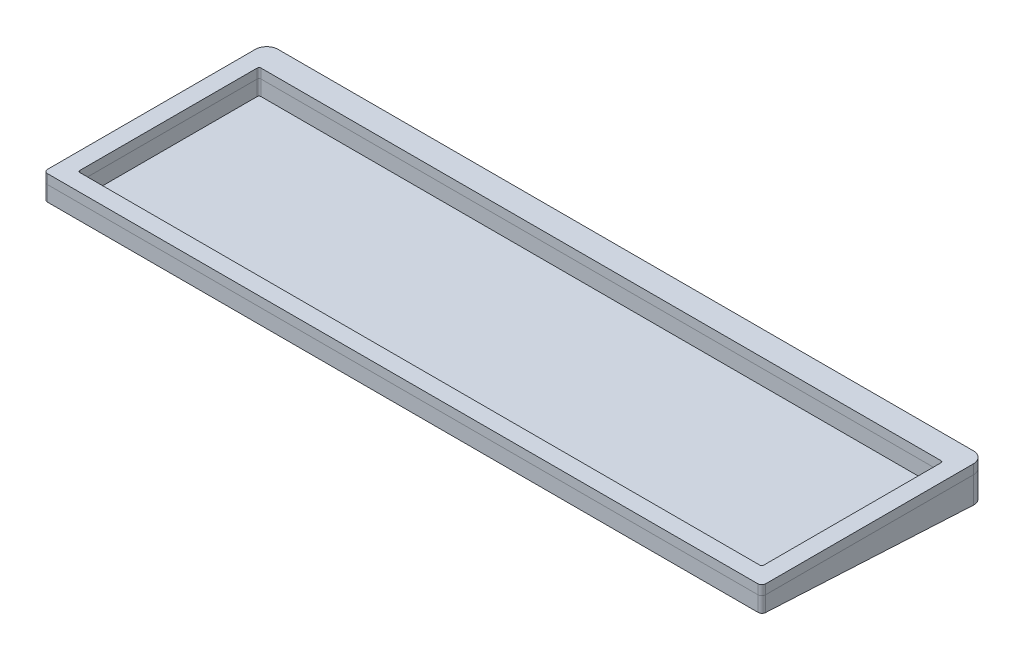
SolidWorks part; units mm, degrees
ref_plane "Front Plane" through (0, 0, 0) normal (0, 0, 1) x (1, 0, 0)
ref_plane "Top Plane" through (0, 0, 0) normal (0, 1, 0) x (1, 0, 0)
ref_plane "Right Plane" through (0, 0, 0) normal (1, 0, 0) x (0, 0, -1)
sketch "Sketch1" plane through (0, 0, 0) normal (0, 1, 0) x (1, 0, 0)
  line L1 (-178.825, 47.625) -> (178.825, 47.625)
  line L2 (-179.825, 46.625) -> (-179.825, -46.625)
  line L3 (-178.825, -47.625) -> (178.825, -47.625)
  line L4 (179.825, 46.625) -> (179.825, -46.625)
  line L5 (-179.825, 47.625) -> (179.825, -47.625) construction
  line L6 (-179.825, -47.625) -> (179.825, 47.625) construction
  arc A0 (178.825, -47.625) -> (179.825, -46.625) centre (178.825, -46.625) ccw
  arc A1 (178.825, 47.625) -> (179.825, 46.625) centre (178.825, 46.625) cw
  arc A2 (-179.825, -46.625) -> (-178.825, -47.625) centre (-178.825, -46.625) ccw
  arc A3 (-178.825, 47.625) -> (-179.825, 46.625) centre (-178.825, 46.625) ccw
  circle A4 centre (157.075, 19.175) radius 1.1
  circle A5 centre (136.925, -16.775) radius 1.1
  circle A6 centre (-153.475, 33.725) radius 1.1
  circle A7 centre (17.925, 22.275) radius 1.1
  circle A8 centre (17.875, -35.075) radius 1.1
  circle A9 centre (-130.375, -35.725) radius 1.1
  point P0 (0, 0)
  dimension "D3" = 1
  dimension "D4" = 2.2
  dimension "D7" = 2.2
  dimension "D8" = 2.2
  dimension "D9" = 2.2
  dimension "D10" = 2.2
  dimension "D11" = 2.2
  dimension "D1" = 359.65
  dimension "D2" = 95.25
  dimension "D5" = 22.75
  dimension "D6" = 28.45
  dimension "D12" = 42.9
  dimension "D13" = 30.85
  dimension "D14" = 25.35
  dimension "D15" = 161.9
  dimension "D16" = 12.55
  dimension "D17" = 161.95
  dimension "D18" = 11.9
  dimension "D19" = 49.45
  dimension "D20" = 13.9
  dimension "D21" = 26.35
sketch "Sketch2" plane through (0, 0, 0) normal (0, 1, 0) x (1, 0, 0)
  line L0 (-179.825, 46.625) -> (-179.825, -46.625) construction
  line L1 (-178.825, -47.625) -> (178.825, -47.625) construction
  line L2 (179.825, 46.625) -> (179.825, -46.625) construction
  line L3 (-178.825, 47.625) -> (178.825, 47.625) construction
  line L4 (-179.825, 46.625) -> (-179.825, -46.625)
  line L5 (-178.825, -47.625) -> (178.825, -47.625)
  line L6 (179.825, 46.625) -> (179.825, -46.625)
  line L7 (-178.825, 47.625) -> (178.825, 47.625)
  line L9 (-182.825, 60.625) -> (182.825, 60.625)
  line L10 (-188.825, 54.625) -> (-188.825, -54.625)
  line L11 (-186.825, -56.625) -> (186.825, -56.625)
  line L12 (188.825, 54.625) -> (188.825, -54.625)
  circle A0 centre (157.075, 19.175) radius 1.1 construction
  circle A1 centre (136.925, -16.775) radius 1.1 construction
  circle A2 centre (17.875, -35.075) radius 1.1 construction
  circle A3 centre (17.925, 22.275) radius 1.1 construction
  circle A4 centre (-153.475, 33.725) radius 1.1 construction
  circle A5 centre (-130.375, -35.725) radius 1.1 construction
  arc A6 (-179.825, -46.625) -> (-178.825, -47.625) centre (-178.825, -46.625) ccw construction
  arc A7 (178.825, -47.625) -> (179.825, -46.625) centre (178.825, -46.625) ccw construction
  arc A8 (179.825, 46.625) -> (178.825, 47.625) centre (178.825, 46.625) ccw construction
  arc A9 (-178.825, 47.625) -> (-179.825, 46.625) centre (-178.825, 46.625) ccw construction
  circle A10 centre (157.075, 19.175) radius 1.1
  circle A11 centre (136.925, -16.775) radius 1.1
  circle A12 centre (17.875, -35.075) radius 1.1
  circle A13 centre (17.925, 22.275) radius 1.1
  circle A14 centre (-153.475, 33.725) radius 1.1
  circle A15 centre (-130.375, -35.725) radius 1.1
  arc A16 (-179.825, -46.625) -> (-178.825, -47.625) centre (-178.825, -46.625) ccw
  arc A17 (178.825, -47.625) -> (179.825, -46.625) centre (178.825, -46.625) ccw
  arc A18 (179.825, 46.625) -> (178.825, 47.625) centre (178.825, 46.625) ccw
  arc A19 (-178.825, 47.625) -> (-179.825, 46.625) centre (-178.825, 46.625) ccw
  arc A20 (182.825, 60.625) -> (188.825, 54.625) centre (182.825, 54.625) cw
  arc A21 (-182.825, 60.625) -> (-188.825, 54.625) centre (-182.825, 54.625) ccw
  arc A22 (186.825, -56.625) -> (188.825, -54.625) centre (186.825, -54.625) ccw
  arc A23 (-188.825, -54.625) -> (-186.825, -56.625) centre (-186.825, -54.625) ccw
  point P30 (0, 0)
  dimension "D5" = 6
  dimension "D6" = 2
  dimension "D1" = 13
  dimension "D2" = 9
  dimension "D3" = 9
  dimension "D4" = 9
extrude "Boss-Extrude1" add sketch "Sketch2" along normal blind 13 contours L10 A23 L11 A22 L12 A20 L9 A21 A19 L7 A18 L6 A17 L5 A16 L4 region at (0, 0, -56.6707)
sketch "Sketch4" plane through (0, 0, 0) normal (0, -1, 0) x (1, 0, 0)
  line L0 (188.825, -54.625) -> (188.825, 54.625) construction
  line L1 (-182.825, -60.625) -> (182.825, -60.625) construction
  line L2 (-188.825, -54.625) -> (-188.825, 54.625) construction
  line L3 (-186.825, 56.625) -> (186.825, 56.625) construction
  line L4 (-179.825, 46.625) -> (-179.825, -46.625)
  line L5 (178.825, 47.625) -> (-178.825, 47.625)
  line L6 (179.825, -46.625) -> (179.825, 46.625)
  line L7 (-178.825, -47.625) -> (178.825, -47.625)
  line L8 (-179.825, 46.625) -> (-179.825, -46.625)
  line L10 (179.825, -46.625) -> (179.825, 46.625)
  line L11 (-178.825, -47.625) -> (178.825, -47.625)
  line L12 (188.825, -54.625) -> (188.825, 54.625)
  line L13 (-182.825, -60.625) -> (182.825, -60.625)
  line L14 (-188.825, -54.625) -> (-188.825, 54.625)
  line L15 (-186.825, 56.625) -> (186.825, 56.625)
  arc A0 (188.825, 54.625) -> (186.825, 56.625) centre (186.825, 54.625) ccw construction
  arc A1 (182.825, -60.625) -> (188.825, -54.625) centre (182.825, -54.625) ccw construction
  arc A2 (-188.825, -54.625) -> (-182.825, -60.625) centre (-182.825, -54.625) ccw construction
  arc A3 (-186.825, 56.625) -> (-188.825, 54.625) centre (-186.825, 54.625) ccw construction
  arc A4 (-179.825, -46.625) -> (-178.825, -47.625) centre (-178.825, -46.625) ccw
  arc A5 (-178.825, 47.625) -> (-179.825, 46.625) centre (-178.825, 46.625) ccw
  arc A6 (179.825, 46.625) -> (178.825, 47.625) centre (178.825, 46.625) ccw
  arc A7 (178.825, -47.625) -> (179.825, -46.625) centre (178.825, -46.625) ccw
  arc A8 (-179.825, -46.625) -> (-178.825, -47.625) centre (-178.825, -46.625) ccw
  arc A9 (-178.825, 47.625) -> (-179.825, 46.625) centre (-178.825, 46.625) ccw
  arc A10 (179.825, 46.625) -> (178.825, 47.625) centre (178.825, 46.625) ccw
  arc A11 (178.825, -47.625) -> (179.825, -46.625) centre (178.825, -46.625) ccw
  arc A12 (188.825, 54.625) -> (186.825, 56.625) centre (186.825, 54.625) ccw
  arc A13 (182.825, -60.625) -> (188.825, -54.625) centre (182.825, -54.625) ccw
  arc A14 (-188.825, -54.625) -> (-182.825, -60.625) centre (-182.825, -54.625) ccw
  arc A15 (-186.825, 56.625) -> (-188.825, 54.625) centre (-186.825, 54.625) ccw
  arc M9 (-178.825, -47.625) -> (-179.825, -46.625) centre (-178.825, -46.625) cw
  line M10 (-179.825, -46.625) -> (-179.825, 46.625)
  arc M11 (-179.825, 46.625) -> (-178.825, 47.625) centre (-178.825, 46.625) cw
  line M12 (-178.825, 47.625) -> (178.825, 47.625)
  arc M13 (178.825, 47.625) -> (179.825, 46.625) centre (178.825, 46.625) cw
  line M14 (179.825, 46.625) -> (179.825, -46.625)
  arc M15 (179.825, -46.625) -> (178.825, -47.625) centre (178.825, -46.625) cw
  line M16 (178.825, -47.625) -> (-178.825, -47.625)
  line M17 (-188.825, 54.625) -> (-188.825, -54.625)
  arc M18 (-188.825, -54.625) -> (-182.825, -60.625) centre (-182.825, -54.625) ccw
  line M19 (-182.825, -60.625) -> (182.825, -60.625)
  arc M20 (182.825, -60.625) -> (188.825, -54.625) centre (182.825, -54.625) ccw
  line M21 (188.825, -54.625) -> (188.825, 54.625)
  arc M22 (188.825, 54.625) -> (186.825, 56.625) centre (186.825, 54.625) ccw
  line M23 (186.825, 56.625) -> (-186.825, 56.625)
  arc M24 (-186.825, 56.625) -> (-188.825, 54.625) centre (-186.825, 54.625) ccw
  dimension "D1" = 0
extrude "Boss-Extrude3" add sketch "Sketch4" along normal blind 10.5 contours M24 M17 M18 M19 M20 M21 M22 M23 M16 M9 M10 M11 M12 M13 M14 M15 | M9 M16 M15 M14 M13 M12 M11 M10 region at (0, 0, 0) region at (184.2715, 0, -56.0715)
sketch "Sketch8" plane through (-188.825, 0, 0) normal (-1, 0, 0) x (0, 0, 1)
  line L0 (54.625, 0) -> (-57.625, 0) construction
  line L2 (-60.625, 13) -> (-60.625, -10.5) construction
  line L4 (-60.625, -6.1448) -> (-60.625, -10.5)
  line L5 (-60.625, -10.5) -> (56.625, -10.5)
  line L11 (56.625, 0) -> (56.625, -10.5)
  line L12 (56.625, 13) -> (56.625, -10.5) construction
  line L13 (-60.625, -6.1448) -> (56.625, 0)
  dimension "D1" = 2
  dimension "D2" = 10.5
  dimension "D3" = 87
extrude "Cut-Extrude4" cut sketch "Sketch8" against normal blind 400
sketch "Sketch9" plane through (0, 0, 0) normal (0, 1, 0) x (1, 0, 0)
  line L0 (-121.9453, 45.1) -> (-108.9453, 45.1)
  line L1 (-121.9453, 31.1) -> (-108.9453, 31.1)
  line L2 (-122.4453, 44.6) -> (-122.4453, 31.6)
  line L3 (-108.4453, 44.6) -> (-108.4453, 31.6)
  line L4 (-102.8953, 45.1) -> (-89.8953, 45.1)
  line L5 (-102.8953, 31.1) -> (-89.8953, 31.1)
  line L6 (-103.3953, 44.6) -> (-103.3953, 31.6)
  line L7 (-89.3953, 44.6) -> (-89.3953, 31.6)
  line L8 (-83.8453, 45.1) -> (-70.8453, 45.1)
  line L9 (-83.8453, 31.1) -> (-70.8453, 31.1)
  line L10 (-84.3453, 44.6) -> (-84.3453, 31.6)
  line L11 (-70.3453, 44.6) -> (-70.3453, 31.6)
  line L12 (-64.7953, 45.1) -> (-51.7953, 45.1)
  line L13 (-64.7953, 31.1) -> (-51.7953, 31.1)
  line L14 (-65.2953, 44.6) -> (-65.2953, 31.6)
  line L15 (-51.2953, 44.6) -> (-51.2953, 31.6)
  line L16 (-45.7453, 45.1) -> (-32.7453, 45.1)
  line L17 (-45.7453, 31.1) -> (-32.7453, 31.1)
  line L18 (-46.2453, 44.6) -> (-46.2453, 31.6)
  line L19 (-32.2453, 44.6) -> (-32.2453, 31.6)
  line L20 (-26.6953, 45.1) -> (-13.6953, 45.1)
  line L21 (-26.6953, 31.1) -> (-13.6953, 31.1)
  line L22 (-27.1953, 44.6) -> (-27.1953, 31.6)
  line L23 (-13.1953, 44.6) -> (-13.1953, 31.6)
  line L24 (-7.6453, 45.1) -> (5.3547, 45.1)
  line L25 (-7.6453, 31.1) -> (5.3547, 31.1)
  line L26 (-8.1453, 44.6) -> (-8.1453, 31.6)
  line L27 (5.8547, 44.6) -> (5.8547, 31.6)
  line L28 (11.4047, 45.1) -> (24.4047, 45.1)
  line L29 (11.4047, 31.1) -> (24.4047, 31.1)
  line L30 (10.9047, 44.6) -> (10.9047, 31.6)
  line L31 (24.9047, 44.6) -> (24.9047, 31.6)
  line L32 (30.4547, 45.1) -> (43.4547, 45.1)
  line L33 (30.4547, 31.1) -> (43.4547, 31.1)
  line L34 (29.9547, 44.6) -> (29.9547, 31.6)
  line L35 (43.9547, 44.6) -> (43.9547, 31.6)
  line L36 (49.5047, 45.1) -> (62.5047, 45.1)
  line L37 (49.5047, 31.1) -> (62.5047, 31.1)
  line L38 (49.0047, 44.6) -> (49.0047, 31.6)
  line L39 (63.0047, 44.6) -> (63.0047, 31.6)
  line L40 (68.5547, 45.1) -> (81.5547, 45.1)
  line L41 (68.5547, 31.1) -> (81.5547, 31.1)
  line L42 (68.0547, 44.6) -> (68.0547, 31.6)
  line L43 (82.0547, 44.6) -> (82.0547, 31.6)
  line L44 (87.6047, 45.1) -> (100.6047, 45.1)
  line L45 (87.6047, 31.1) -> (100.6047, 31.1)
  line L46 (87.1047, 44.6) -> (87.1047, 31.6)
  line L47 (101.1047, 44.6) -> (101.1047, 31.6)
  line L48 (106.6547, 45.1) -> (119.6547, 45.1)
  line L49 (106.6547, 31.1) -> (119.6547, 31.1)
  line L50 (106.1547, 44.6) -> (106.1547, 31.6)
  line L51 (120.1547, 44.6) -> (120.1547, 31.6)
  line L52 (135.2297, 45.1) -> (148.2297, 45.1)
  line L53 (135.2297, 31.1) -> (148.2297, 31.1)
  line L54 (134.7297, 44.6) -> (134.7297, 31.6)
  line L55 (148.7297, 44.6) -> (148.7297, 31.6)
  line L56 (150.6677, 44.1) -> (156.6677, 44.1)
  line L57 (150.6677, 29.1) -> (156.6677, 29.1)
  line L58 (150.1677, 43.6) -> (150.1677, 29.6)
  line L59 (157.1677, 43.6) -> (157.1677, 29.6)
  line L60 (126.7917, 44.1) -> (132.7917, 44.1)
  line L61 (126.7917, 29.1) -> (132.7917, 29.1)
  line L62 (126.2917, 43.6) -> (126.2917, 29.6)
  line L63 (133.2917, 43.6) -> (133.2917, 29.6)
  line L64 (163.8047, 45.1) -> (176.8047, 45.1)
  line L65 (163.8047, 31.1) -> (176.8047, 31.1)
  line L66 (163.3047, 44.6) -> (163.3047, 31.6)
  line L67 (177.3047, 44.6) -> (177.3047, 31.6)
  line L68 (-117.1828, 26.05) -> (-104.1828, 26.05)
  line L69 (-117.1828, 12.05) -> (-104.1828, 12.05)
  line L70 (-117.6828, 25.55) -> (-117.6828, 12.55)
  line L71 (-103.6828, 25.55) -> (-103.6828, 12.55)
  line L72 (-93.3703, 26.05) -> (-80.3703, 26.05)
  line L73 (-93.3703, 12.05) -> (-80.3703, 12.05)
  line L74 (-93.8703, 25.55) -> (-93.8703, 12.55)
  line L75 (-79.8703, 25.55) -> (-79.8703, 12.55)
  line L76 (-74.3203, 26.05) -> (-61.3203, 26.05)
  line L77 (-74.3203, 12.05) -> (-61.3203, 12.05)
  line L78 (-74.8203, 25.55) -> (-74.8203, 12.55)
  line L79 (-60.8203, 25.55) -> (-60.8203, 12.55)
  line L80 (-55.2703, 26.05) -> (-42.2703, 26.05)
  line L81 (-55.2703, 12.05) -> (-42.2703, 12.05)
  line L82 (-55.7703, 25.55) -> (-55.7703, 12.55)
  line L83 (-41.7703, 25.55) -> (-41.7703, 12.55)
  line L84 (-36.2203, 26.05) -> (-23.2203, 26.05)
  line L85 (-36.2203, 12.05) -> (-23.2203, 12.05)
  line L86 (-36.7203, 25.55) -> (-36.7203, 12.55)
  line L87 (-22.7203, 25.55) -> (-22.7203, 12.55)
  line L88 (-17.1703, 26.05) -> (-4.1703, 26.05)
  line L89 (-17.1703, 12.05) -> (-4.1703, 12.05)
  line L90 (-17.6703, 25.55) -> (-17.6703, 12.55)
  line L91 (-3.6703, 25.55) -> (-3.6703, 12.55)
  line L92 (1.8797, 26.05) -> (14.8797, 26.05)
  line L93 (1.8797, 12.05) -> (14.8797, 12.05)
  line L94 (1.3797, 25.55) -> (1.3797, 12.55)
  line L95 (15.3797, 25.55) -> (15.3797, 12.55)
  line L96 (20.9297, 26.05) -> (33.9297, 26.05)
  line L97 (20.9297, 12.05) -> (33.9297, 12.05)
  line L98 (20.4297, 25.55) -> (20.4297, 12.55)
  line L99 (34.4297, 25.55) -> (34.4297, 12.55)
  line L100 (39.9797, 26.05) -> (52.9797, 26.05)
  line L101 (39.9797, 12.05) -> (52.9797, 12.05)
  line L102 (39.4797, 25.55) -> (39.4797, 12.55)
  line L103 (53.4797, 25.55) -> (53.4797, 12.55)
  line L104 (59.0297, 26.05) -> (72.0297, 26.05)
  line L105 (59.0297, 12.05) -> (72.0297, 12.05)
  line L106 (58.5297, 25.55) -> (58.5297, 12.55)
  line L107 (72.5297, 25.55) -> (72.5297, 12.55)
  line L108 (78.0797, 26.05) -> (91.0797, 26.05)
  line L109 (78.0797, 12.05) -> (91.0797, 12.05)
  line L110 (77.5797, 25.55) -> (77.5797, 12.55)
  line L111 (91.5797, 25.55) -> (91.5797, 12.55)
  line L112 (97.1297, 26.05) -> (110.1297, 26.05)
  line L113 (97.1297, 12.05) -> (110.1297, 12.05)
  line L114 (96.6297, 25.55) -> (96.6297, 12.55)
  line L115 (110.6297, 25.55) -> (110.6297, 12.55)
  line L116 (116.1797, 26.05) -> (129.1797, 26.05)
  line L117 (116.1797, 12.05) -> (129.1797, 12.05)
  line L118 (115.6797, 25.55) -> (115.6797, 12.55)
  line L119 (129.6797, 25.55) -> (129.6797, 12.55)
  line L120 (139.9922, 26.05) -> (152.9922, 26.05)
  line L121 (139.9922, 12.05) -> (152.9922, 12.05)
  line L122 (139.4922, 25.55) -> (139.4922, 12.55)
  line L123 (153.4922, 25.55) -> (153.4922, 12.55)
  line L124 (163.8047, 26.05) -> (176.8047, 26.05)
  line L125 (163.8047, 12.05) -> (176.8047, 12.05)
  line L126 (163.3047, 25.55) -> (163.3047, 12.55)
  line L127 (177.3047, 25.55) -> (177.3047, 12.55)
  line L128 (-114.8016, 7) -> (-101.8016, 7)
  line L129 (-114.8016, -7) -> (-101.8016, -7)
  line L130 (-115.3016, 6.5) -> (-115.3016, -6.5)
  line L131 (-101.3016, 6.5) -> (-101.3016, -6.5)
  line L132 (-88.6078, 7) -> (-75.6078, 7)
  line L133 (-88.6078, -7) -> (-75.6078, -7)
  line L134 (-89.1078, 6.5) -> (-89.1078, -6.5)
  line L135 (-75.1078, 6.5) -> (-75.1078, -6.5)
  line L136 (-69.5578, 7) -> (-56.5578, 7)
  line L137 (-69.5578, -7) -> (-56.5578, -7)
  line L138 (-70.0578, 6.5) -> (-70.0578, -6.5)
  line L139 (-56.0578, 6.5) -> (-56.0578, -6.5)
  line L140 (-50.5078, 7) -> (-37.5078, 7)
  line L141 (-50.5078, -7) -> (-37.5078, -7)
  line L142 (-51.0078, 6.5) -> (-51.0078, -6.5)
  line L143 (-37.0078, 6.5) -> (-37.0078, -6.5)
  line L144 (-31.4578, 7) -> (-18.4578, 7)
  line L145 (-31.4578, -7) -> (-18.4578, -7)
  line L146 (-31.9578, 6.5) -> (-31.9578, -6.5)
  line L147 (-17.9578, 6.5) -> (-17.9578, -6.5)
  line L148 (-12.4078, 7) -> (0.5922, 7)
  line L149 (-12.4078, -7) -> (0.5922, -7)
  line L150 (-12.9078, 6.5) -> (-12.9078, -6.5)
  line L151 (1.0922, 6.5) -> (1.0922, -6.5)
  line L152 (6.6422, 7) -> (19.6422, 7)
  line L153 (6.6422, -7) -> (19.6422, -7)
  line L154 (6.1422, 6.5) -> (6.1422, -6.5)
  line L155 (20.1422, 6.5) -> (20.1422, -6.5)
  line L156 (25.6922, 7) -> (38.6922, 7)
  line L157 (25.6922, -7) -> (38.6922, -7)
  line L158 (25.1922, 6.5) -> (25.1922, -6.5)
  line L159 (39.1922, 6.5) -> (39.1922, -6.5)
  line L160 (44.7422, 7) -> (57.7422, 7)
  line L161 (44.7422, -7) -> (57.7422, -7)
  line L162 (44.2422, 6.5) -> (44.2422, -6.5)
  line L163 (58.2422, 6.5) -> (58.2422, -6.5)
  line L164 (63.7922, 7) -> (76.7922, 7)
  line L165 (63.7922, -7) -> (76.7922, -7)
  line L166 (63.2922, 6.5) -> (63.2922, -6.5)
  line L167 (77.2922, 6.5) -> (77.2922, -6.5)
  line L168 (82.8422, 7) -> (95.8422, 7)
  line L169 (82.8422, -7) -> (95.8422, -7)
  line L170 (82.3422, 6.5) -> (82.3422, -6.5)
  line L171 (96.3422, 6.5) -> (96.3422, -6.5)
  line L172 (101.8922, 7) -> (114.8922, 7)
  line L173 (101.8922, -7) -> (114.8922, -7)
  line L174 (101.3922, 6.5) -> (101.3922, -6.5)
  line L175 (115.3922, 6.5) -> (115.3922, -6.5)
  line L176 (132.8484, 7) -> (145.8484, 7)
  line L177 (132.8484, -7) -> (145.8484, -7)
  line L178 (132.3484, 6.5) -> (132.3484, -6.5)
  line L179 (146.3484, 6.5) -> (146.3484, -6.5)
  line L180 (148.2864, 6) -> (154.2864, 6)
  line L181 (148.2864, -9) -> (154.2864, -9)
  line L182 (147.7864, 5.5) -> (147.7864, -8.5)
  line L183 (154.7864, 5.5) -> (154.7864, -8.5)
  line L184 (124.4104, 6) -> (130.4104, 6)
  line L185 (124.4104, -9) -> (130.4104, -9)
  line L186 (123.9104, 5.5) -> (123.9104, -8.5)
  line L187 (130.9104, 5.5) -> (130.9104, -8.5)
  line L188 (163.8047, 7) -> (176.8047, 7)
  line L189 (163.8047, -7) -> (176.8047, -7)
  line L190 (163.3047, 6.5) -> (163.3047, -6.5)
  line L191 (177.3047, 6.5) -> (177.3047, -6.5)
  line L192 (-110.0391, -12.05) -> (-97.0391, -12.05)
  line L193 (-110.0391, -26.05) -> (-97.0391, -26.05)
  line L194 (-110.5391, -12.55) -> (-110.5391, -25.55)
  line L195 (-96.5391, -12.55) -> (-96.5391, -25.55)
  line L196 (-94.6011, -13.05) -> (-88.6011, -13.05)
  line L197 (-94.6011, -28.05) -> (-88.6011, -28.05)
  line L198 (-95.1011, -13.55) -> (-95.1011, -27.55)
  line L199 (-88.1011, -13.55) -> (-88.1011, -27.55)
  line L200 (-118.4771, -13.05) -> (-112.4771, -13.05)
  line L201 (-118.4771, -28.05) -> (-112.4771, -28.05)
  line L202 (-118.9771, -13.55) -> (-118.9771, -27.55)
  line L203 (-111.9771, -13.55) -> (-111.9771, -27.55)
  line L204 (-79.0828, -12.05) -> (-66.0828, -12.05)
  line L205 (-79.0828, -26.05) -> (-66.0828, -26.05)
  line L206 (-79.5828, -12.55) -> (-79.5828, -25.55)
  line L207 (-65.5828, -12.55) -> (-65.5828, -25.55)
  line L208 (-60.0328, -12.05) -> (-47.0328, -12.05)
  line L209 (-60.0328, -26.05) -> (-47.0328, -26.05)
  line L210 (-60.5328, -12.55) -> (-60.5328, -25.55)
  line L211 (-46.5328, -12.55) -> (-46.5328, -25.55)
  line L212 (-40.9828, -12.05) -> (-27.9828, -12.05)
  line L213 (-40.9828, -26.05) -> (-27.9828, -26.05)
  line L214 (-41.4828, -12.55) -> (-41.4828, -25.55)
  line L215 (-27.4828, -12.55) -> (-27.4828, -25.55)
  line L216 (-21.9328, -12.05) -> (-8.9328, -12.05)
  line L217 (-21.9328, -26.05) -> (-8.9328, -26.05)
  line L218 (-22.4328, -12.55) -> (-22.4328, -25.55)
  line L219 (-8.4328, -12.55) -> (-8.4328, -25.55)
  line L220 (-2.8828, -12.05) -> (10.1172, -12.05)
  line L221 (-2.8828, -26.05) -> (10.1172, -26.05)
  line L222 (-3.3828, -12.55) -> (-3.3828, -25.55)
  line L223 (10.6172, -12.55) -> (10.6172, -25.55)
  line L224 (16.1672, -12.05) -> (29.1672, -12.05)
  line L225 (16.1672, -26.05) -> (29.1672, -26.05)
  line L226 (15.6672, -12.55) -> (15.6672, -25.55)
  line L227 (29.6672, -12.55) -> (29.6672, -25.55)
  line L228 (35.2172, -12.05) -> (48.2172, -12.05)
  line L229 (35.2172, -26.05) -> (48.2172, -26.05)
  line L230 (34.7172, -12.55) -> (34.7172, -25.55)
  line L231 (48.7172, -12.55) -> (48.7172, -25.55)
  line L232 (54.2672, -12.05) -> (67.2672, -12.05)
  line L233 (54.2672, -26.05) -> (67.2672, -26.05)
  line L234 (53.7672, -12.55) -> (53.7672, -25.55)
  line L235 (67.7672, -12.55) -> (67.7672, -25.55)
  line L236 (73.3172, -12.05) -> (86.3172, -12.05)
  line L237 (73.3172, -26.05) -> (86.3172, -26.05)
  line L238 (72.8172, -12.55) -> (72.8172, -25.55)
  line L239 (86.8172, -12.55) -> (86.8172, -25.55)
  line L240 (92.3672, -12.05) -> (105.3672, -12.05)
  line L241 (92.3672, -26.05) -> (105.3672, -26.05)
  line L242 (91.8672, -12.55) -> (91.8672, -25.55)
  line L243 (105.8672, -12.55) -> (105.8672, -25.55)
  line L244 (118.5609, -12.05) -> (131.5609, -12.05)
  line L245 (118.5609, -26.05) -> (131.5609, -26.05)
  line L246 (118.0609, -12.55) -> (118.0609, -25.55)
  line L247 (132.0609, -12.55) -> (132.0609, -25.55)
  line L248 (144.7547, -12.05) -> (157.7547, -12.05)
  line L249 (144.7547, -26.05) -> (157.7547, -26.05)
  line L250 (144.2547, -12.55) -> (144.2547, -25.55)
  line L251 (158.2547, -12.55) -> (158.2547, -25.55)
  line L252 (163.8047, -12.05) -> (176.8047, -12.05)
  line L253 (163.8047, -26.05) -> (176.8047, -26.05)
  line L254 (163.3047, -12.55) -> (163.3047, -25.55)
  line L255 (177.3047, -12.55) -> (177.3047, -25.55)
  line L256 (-119.5641, -31.1) -> (-106.5641, -31.1)
  line L257 (-119.5641, -45.1) -> (-106.5641, -45.1)
  line L258 (-120.0641, -31.6) -> (-120.0641, -44.6)
  line L259 (-106.0641, -31.6) -> (-106.0641, -44.6)
  line L260 (-95.7516, -31.1) -> (-82.7516, -31.1)
  line L261 (-95.7516, -45.1) -> (-82.7516, -45.1)
  line L262 (-96.2516, -31.6) -> (-96.2516, -44.6)
  line L263 (-82.2516, -31.6) -> (-82.2516, -44.6)
  line L264 (-71.9391, -31.1) -> (-58.9391, -31.1)
  line L265 (-71.9391, -45.1) -> (-58.9391, -45.1)
  line L266 (-72.4391, -31.6) -> (-72.4391, -44.6)
  line L267 (-58.4391, -31.6) -> (-58.4391, -44.6)
  line L268 (-0.5016, -31.1) -> (12.4984, -31.1)
  line L269 (-0.5016, -45.1) -> (12.4984, -45.1)
  line L270 (-1.0016, -31.6) -> (-1.0016, -44.6)
  line L271 (12.9984, -31.6) -> (12.9984, -44.6)
  line L272 (52.9984, -32.1) -> (58.9984, -32.1)
  line L273 (52.9984, -47.1) -> (58.9984, -47.1)
  line L274 (52.4984, -32.6) -> (52.4984, -46.6)
  line L275 (59.4984, -32.6) -> (59.4984, -46.6)
  line L276 (-47.0016, -32.1) -> (-41.0016, -32.1)
  line L277 (-47.0016, -47.1) -> (-41.0016, -47.1)
  line L278 (-47.5016, -32.6) -> (-47.5016, -46.6)
  line L279 (-40.5016, -32.6) -> (-40.5016, -46.6)
  line L280 (68.5547, -31.1) -> (81.5547, -31.1)
  line L281 (68.5547, -45.1) -> (81.5547, -45.1)
  line L282 (68.0547, -31.6) -> (68.0547, -44.6)
  line L283 (82.0547, -31.6) -> (82.0547, -44.6)
  line L284 (87.6047, -31.1) -> (100.6047, -31.1)
  line L285 (87.6047, -45.1) -> (100.6047, -45.1)
  line L286 (87.1047, -31.6) -> (87.1047, -44.6)
  line L287 (101.1047, -31.6) -> (101.1047, -44.6)
  line L288 (106.6547, -31.1) -> (119.6547, -31.1)
  line L289 (106.6547, -45.1) -> (119.6547, -45.1)
  line L290 (106.1547, -31.6) -> (106.1547, -44.6)
  line L291 (120.1547, -31.6) -> (120.1547, -44.6)
  line L292 (125.7047, -31.1) -> (138.7047, -31.1)
  line L293 (125.7047, -45.1) -> (138.7047, -45.1)
  line L294 (125.2047, -31.6) -> (125.2047, -44.6)
  line L295 (139.2047, -31.6) -> (139.2047, -44.6)
  line L296 (144.7547, -31.1) -> (157.7547, -31.1)
  line L297 (144.7547, -45.1) -> (157.7547, -45.1)
  line L298 (144.2547, -31.6) -> (144.2547, -44.6)
  line L299 (158.2547, -31.6) -> (158.2547, -44.6)
  line L300 (163.8047, -31.1) -> (176.8047, -31.1)
  line L301 (163.8047, -45.1) -> (176.8047, -45.1)
  line L302 (163.3047, -31.6) -> (163.3047, -44.6)
  line L303 (177.3047, -31.6) -> (177.3047, -44.6)
  line L304 (-124.9703, 47.625) -> (-103.2456, 47.625)
  line L305 (-124.9703, -47.625) -> (179.8297, -47.625)
  line L306 (-124.9703, 47.625) -> (-124.9703, -47.625)
  line L307 (179.8297, 47.625) -> (179.8297, -47.625)
  line L308 (-103.2456, 53.125) -> (-103.2456, 47.625)
  line L309 (-124.9703, 47.625) -> (-103.2456, 47.625)
  line L311 (-101.2456, 55.125) -> (-90.2456, 55.125)
  line L312 (-88.2456, 47.625) -> (-88.2456, 53.125)
  line L313 (-23.2456, 53.125) -> (-23.2456, 47.625)
  line L314 (-21.2456, 55.125) -> (-10.2456, 55.125)
  line L315 (-8.2456, 47.625) -> (-8.2456, 53.125)
  line L316 (56.7544, 53.125) -> (56.7544, 47.625)
  line L317 (58.7544, 55.125) -> (69.7544, 55.125)
  line L318 (71.7544, 47.625) -> (71.7544, 53.125)
  line L319 (136.7544, 53.125) -> (136.7544, 47.625)
  line L320 (138.7544, 55.125) -> (149.7544, 55.125)
  line L321 (151.7544, 47.625) -> (151.7544, 53.125)
  line L322 (-88.2456, 47.625) -> (-23.2456, 47.625)
  line L323 (-8.2456, 47.625) -> (56.7544, 47.625)
  line L324 (71.7544, 47.625) -> (136.7544, 47.625)
  line L325 (151.7544, 47.625) -> (179.8297, 47.625)
  arc A0 (-121.9453, 45.1) -> (-122.4453, 44.6) centre (-121.9453, 44.6) ccw
  arc A1 (-108.4453, 44.6) -> (-108.9453, 45.1) centre (-108.9453, 44.6) ccw
  arc A2 (-122.4453, 31.6) -> (-121.9453, 31.1) centre (-121.9453, 31.6) ccw
  arc A3 (-108.9453, 31.1) -> (-108.4453, 31.6) centre (-108.9453, 31.6) ccw
  arc A4 (-102.8953, 45.1) -> (-103.3953, 44.6) centre (-102.8953, 44.6) ccw
  arc A5 (-89.3953, 44.6) -> (-89.8953, 45.1) centre (-89.8953, 44.6) ccw
  arc A6 (-103.3953, 31.6) -> (-102.8953, 31.1) centre (-102.8953, 31.6) ccw
  arc A7 (-89.8953, 31.1) -> (-89.3953, 31.6) centre (-89.8953, 31.6) ccw
  arc A8 (-83.8453, 45.1) -> (-84.3453, 44.6) centre (-83.8453, 44.6) ccw
  arc A9 (-70.3453, 44.6) -> (-70.8453, 45.1) centre (-70.8453, 44.6) ccw
  arc A10 (-84.3453, 31.6) -> (-83.8453, 31.1) centre (-83.8453, 31.6) ccw
  arc A11 (-70.8453, 31.1) -> (-70.3453, 31.6) centre (-70.8453, 31.6) ccw
  arc A12 (-64.7953, 45.1) -> (-65.2953, 44.6) centre (-64.7953, 44.6) ccw
  arc A13 (-51.2953, 44.6) -> (-51.7953, 45.1) centre (-51.7953, 44.6) ccw
  arc A14 (-65.2953, 31.6) -> (-64.7953, 31.1) centre (-64.7953, 31.6) ccw
  arc A15 (-51.7953, 31.1) -> (-51.2953, 31.6) centre (-51.7953, 31.6) ccw
  arc A16 (-45.7453, 45.1) -> (-46.2453, 44.6) centre (-45.7453, 44.6) ccw
  arc A17 (-32.2453, 44.6) -> (-32.7453, 45.1) centre (-32.7453, 44.6) ccw
  arc A18 (-46.2453, 31.6) -> (-45.7453, 31.1) centre (-45.7453, 31.6) ccw
  arc A19 (-32.7453, 31.1) -> (-32.2453, 31.6) centre (-32.7453, 31.6) ccw
  arc A20 (-26.6953, 45.1) -> (-27.1953, 44.6) centre (-26.6953, 44.6) ccw
  arc A21 (-13.1953, 44.6) -> (-13.6953, 45.1) centre (-13.6953, 44.6) ccw
  arc A22 (-27.1953, 31.6) -> (-26.6953, 31.1) centre (-26.6953, 31.6) ccw
  arc A23 (-13.6953, 31.1) -> (-13.1953, 31.6) centre (-13.6953, 31.6) ccw
  arc A24 (-7.6453, 45.1) -> (-8.1453, 44.6) centre (-7.6453, 44.6) ccw
  arc A25 (5.8547, 44.6) -> (5.3547, 45.1) centre (5.3547, 44.6) ccw
  arc A26 (-8.1453, 31.6) -> (-7.6453, 31.1) centre (-7.6453, 31.6) ccw
  arc A27 (5.3547, 31.1) -> (5.8547, 31.6) centre (5.3547, 31.6) ccw
  arc A28 (11.4047, 45.1) -> (10.9047, 44.6) centre (11.4047, 44.6) ccw
  arc A29 (24.9047, 44.6) -> (24.4047, 45.1) centre (24.4047, 44.6) ccw
  arc A30 (10.9047, 31.6) -> (11.4047, 31.1) centre (11.4047, 31.6) ccw
  arc A31 (24.4047, 31.1) -> (24.9047, 31.6) centre (24.4047, 31.6) ccw
  arc A32 (30.4547, 45.1) -> (29.9547, 44.6) centre (30.4547, 44.6) ccw
  arc A33 (43.9547, 44.6) -> (43.4547, 45.1) centre (43.4547, 44.6) ccw
  arc A34 (29.9547, 31.6) -> (30.4547, 31.1) centre (30.4547, 31.6) ccw
  arc A35 (43.4547, 31.1) -> (43.9547, 31.6) centre (43.4547, 31.6) ccw
  arc A36 (49.5047, 45.1) -> (49.0047, 44.6) centre (49.5047, 44.6) ccw
  arc A37 (63.0047, 44.6) -> (62.5047, 45.1) centre (62.5047, 44.6) ccw
  arc A38 (49.0047, 31.6) -> (49.5047, 31.1) centre (49.5047, 31.6) ccw
  arc A39 (62.5047, 31.1) -> (63.0047, 31.6) centre (62.5047, 31.6) ccw
  arc A40 (68.5547, 45.1) -> (68.0547, 44.6) centre (68.5547, 44.6) ccw
  arc A41 (82.0547, 44.6) -> (81.5547, 45.1) centre (81.5547, 44.6) ccw
  arc A42 (68.0547, 31.6) -> (68.5547, 31.1) centre (68.5547, 31.6) ccw
  arc A43 (81.5547, 31.1) -> (82.0547, 31.6) centre (81.5547, 31.6) ccw
  arc A44 (87.6047, 45.1) -> (87.1047, 44.6) centre (87.6047, 44.6) ccw
  arc A45 (101.1047, 44.6) -> (100.6047, 45.1) centre (100.6047, 44.6) ccw
  arc A46 (87.1047, 31.6) -> (87.6047, 31.1) centre (87.6047, 31.6) ccw
  arc A47 (100.6047, 31.1) -> (101.1047, 31.6) centre (100.6047, 31.6) ccw
  arc A48 (106.6547, 45.1) -> (106.1547, 44.6) centre (106.6547, 44.6) ccw
  arc A49 (120.1547, 44.6) -> (119.6547, 45.1) centre (119.6547, 44.6) ccw
  arc A50 (106.1547, 31.6) -> (106.6547, 31.1) centre (106.6547, 31.6) ccw
  arc A51 (119.6547, 31.1) -> (120.1547, 31.6) centre (119.6547, 31.6) ccw
  arc A52 (135.2297, 45.1) -> (134.7297, 44.6) centre (135.2297, 44.6) ccw
  arc A53 (148.7297, 44.6) -> (148.2297, 45.1) centre (148.2297, 44.6) ccw
  arc A54 (134.7297, 31.6) -> (135.2297, 31.1) centre (135.2297, 31.6) ccw
  arc A55 (148.2297, 31.1) -> (148.7297, 31.6) centre (148.2297, 31.6) ccw
  arc A56 (150.6677, 44.1) -> (150.1677, 43.6) centre (150.6677, 43.6) ccw
  arc A57 (157.1677, 43.6) -> (156.6677, 44.1) centre (156.6677, 43.6) ccw
  arc A58 (150.1677, 29.6) -> (150.6677, 29.1) centre (150.6677, 29.6) ccw
  arc A59 (156.6677, 29.1) -> (157.1677, 29.6) centre (156.6677, 29.6) ccw
  arc A60 (126.7917, 44.1) -> (126.2917, 43.6) centre (126.7917, 43.6) ccw
  arc A61 (133.2917, 43.6) -> (132.7917, 44.1) centre (132.7917, 43.6) ccw
  arc A62 (126.2917, 29.6) -> (126.7917, 29.1) centre (126.7917, 29.6) ccw
  arc A63 (132.7917, 29.1) -> (133.2917, 29.6) centre (132.7917, 29.6) ccw
  arc A64 (163.8047, 45.1) -> (163.3047, 44.6) centre (163.8047, 44.6) ccw
  arc A65 (177.3047, 44.6) -> (176.8047, 45.1) centre (176.8047, 44.6) ccw
  arc A66 (163.3047, 31.6) -> (163.8047, 31.1) centre (163.8047, 31.6) ccw
  arc A67 (176.8047, 31.1) -> (177.3047, 31.6) centre (176.8047, 31.6) ccw
  arc A68 (-117.1828, 26.05) -> (-117.6828, 25.55) centre (-117.1828, 25.55) ccw
  arc A69 (-103.6828, 25.55) -> (-104.1828, 26.05) centre (-104.1828, 25.55) ccw
  arc A70 (-117.6828, 12.55) -> (-117.1828, 12.05) centre (-117.1828, 12.55) ccw
  arc A71 (-104.1828, 12.05) -> (-103.6828, 12.55) centre (-104.1828, 12.55) ccw
  arc A72 (-93.3703, 26.05) -> (-93.8703, 25.55) centre (-93.3703, 25.55) ccw
  arc A73 (-79.8703, 25.55) -> (-80.3703, 26.05) centre (-80.3703, 25.55) ccw
  arc A74 (-93.8703, 12.55) -> (-93.3703, 12.05) centre (-93.3703, 12.55) ccw
  arc A75 (-80.3703, 12.05) -> (-79.8703, 12.55) centre (-80.3703, 12.55) ccw
  arc A76 (-74.3203, 26.05) -> (-74.8203, 25.55) centre (-74.3203, 25.55) ccw
  arc A77 (-60.8203, 25.55) -> (-61.3203, 26.05) centre (-61.3203, 25.55) ccw
  arc A78 (-74.8203, 12.55) -> (-74.3203, 12.05) centre (-74.3203, 12.55) ccw
  arc A79 (-61.3203, 12.05) -> (-60.8203, 12.55) centre (-61.3203, 12.55) ccw
  arc A80 (-55.2703, 26.05) -> (-55.7703, 25.55) centre (-55.2703, 25.55) ccw
  arc A81 (-41.7703, 25.55) -> (-42.2703, 26.05) centre (-42.2703, 25.55) ccw
  arc A82 (-55.7703, 12.55) -> (-55.2703, 12.05) centre (-55.2703, 12.55) ccw
  arc A83 (-42.2703, 12.05) -> (-41.7703, 12.55) centre (-42.2703, 12.55) ccw
  arc A84 (-36.2203, 26.05) -> (-36.7203, 25.55) centre (-36.2203, 25.55) ccw
  arc A85 (-22.7203, 25.55) -> (-23.2203, 26.05) centre (-23.2203, 25.55) ccw
  arc A86 (-36.7203, 12.55) -> (-36.2203, 12.05) centre (-36.2203, 12.55) ccw
  arc A87 (-23.2203, 12.05) -> (-22.7203, 12.55) centre (-23.2203, 12.55) ccw
  arc A88 (-17.1703, 26.05) -> (-17.6703, 25.55) centre (-17.1703, 25.55) ccw
  arc A89 (-3.6703, 25.55) -> (-4.1703, 26.05) centre (-4.1703, 25.55) ccw
  arc A90 (-17.6703, 12.55) -> (-17.1703, 12.05) centre (-17.1703, 12.55) ccw
  arc A91 (-4.1703, 12.05) -> (-3.6703, 12.55) centre (-4.1703, 12.55) ccw
  arc A92 (1.8797, 26.05) -> (1.3797, 25.55) centre (1.8797, 25.55) ccw
  arc A93 (15.3797, 25.55) -> (14.8797, 26.05) centre (14.8797, 25.55) ccw
  arc A94 (1.3797, 12.55) -> (1.8797, 12.05) centre (1.8797, 12.55) ccw
  arc A95 (14.8797, 12.05) -> (15.3797, 12.55) centre (14.8797, 12.55) ccw
  arc A96 (20.9297, 26.05) -> (20.4297, 25.55) centre (20.9297, 25.55) ccw
  arc A97 (34.4297, 25.55) -> (33.9297, 26.05) centre (33.9297, 25.55) ccw
  arc A98 (20.4297, 12.55) -> (20.9297, 12.05) centre (20.9297, 12.55) ccw
  arc A99 (33.9297, 12.05) -> (34.4297, 12.55) centre (33.9297, 12.55) ccw
  arc A100 (39.9797, 26.05) -> (39.4797, 25.55) centre (39.9797, 25.55) ccw
  arc A101 (53.4797, 25.55) -> (52.9797, 26.05) centre (52.9797, 25.55) ccw
  arc A102 (39.4797, 12.55) -> (39.9797, 12.05) centre (39.9797, 12.55) ccw
  arc A103 (52.9797, 12.05) -> (53.4797, 12.55) centre (52.9797, 12.55) ccw
  arc A104 (59.0297, 26.05) -> (58.5297, 25.55) centre (59.0297, 25.55) ccw
  arc A105 (72.5297, 25.55) -> (72.0297, 26.05) centre (72.0297, 25.55) ccw
  arc A106 (58.5297, 12.55) -> (59.0297, 12.05) centre (59.0297, 12.55) ccw
  arc A107 (72.0297, 12.05) -> (72.5297, 12.55) centre (72.0297, 12.55) ccw
  arc A108 (78.0797, 26.05) -> (77.5797, 25.55) centre (78.0797, 25.55) ccw
  arc A109 (91.5797, 25.55) -> (91.0797, 26.05) centre (91.0797, 25.55) ccw
  arc A110 (77.5797, 12.55) -> (78.0797, 12.05) centre (78.0797, 12.55) ccw
  arc A111 (91.0797, 12.05) -> (91.5797, 12.55) centre (91.0797, 12.55) ccw
  arc A112 (97.1297, 26.05) -> (96.6297, 25.55) centre (97.1297, 25.55) ccw
  arc A113 (110.6297, 25.55) -> (110.1297, 26.05) centre (110.1297, 25.55) ccw
  arc A114 (96.6297, 12.55) -> (97.1297, 12.05) centre (97.1297, 12.55) ccw
  arc A115 (110.1297, 12.05) -> (110.6297, 12.55) centre (110.1297, 12.55) ccw
  arc A116 (116.1797, 26.05) -> (115.6797, 25.55) centre (116.1797, 25.55) ccw
  arc A117 (129.6797, 25.55) -> (129.1797, 26.05) centre (129.1797, 25.55) ccw
  arc A118 (115.6797, 12.55) -> (116.1797, 12.05) centre (116.1797, 12.55) ccw
  arc A119 (129.1797, 12.05) -> (129.6797, 12.55) centre (129.1797, 12.55) ccw
  arc A120 (139.9922, 26.05) -> (139.4922, 25.55) centre (139.9922, 25.55) ccw
  arc A121 (153.4922, 25.55) -> (152.9922, 26.05) centre (152.9922, 25.55) ccw
  arc A122 (139.4922, 12.55) -> (139.9922, 12.05) centre (139.9922, 12.55) ccw
  arc A123 (152.9922, 12.05) -> (153.4922, 12.55) centre (152.9922, 12.55) ccw
  arc A124 (163.8047, 26.05) -> (163.3047, 25.55) centre (163.8047, 25.55) ccw
  arc A125 (177.3047, 25.55) -> (176.8047, 26.05) centre (176.8047, 25.55) ccw
  arc A126 (163.3047, 12.55) -> (163.8047, 12.05) centre (163.8047, 12.55) ccw
  arc A127 (176.8047, 12.05) -> (177.3047, 12.55) centre (176.8047, 12.55) ccw
  arc A128 (-114.8016, 7) -> (-115.3016, 6.5) centre (-114.8016, 6.5) ccw
  arc A129 (-101.3016, 6.5) -> (-101.8016, 7) centre (-101.8016, 6.5) ccw
  arc A130 (-115.3016, -6.5) -> (-114.8016, -7) centre (-114.8016, -6.5) ccw
  arc A131 (-101.8016, -7) -> (-101.3016, -6.5) centre (-101.8016, -6.5) ccw
  arc A132 (-88.6078, 7) -> (-89.1078, 6.5) centre (-88.6078, 6.5) ccw
  arc A133 (-75.1078, 6.5) -> (-75.6078, 7) centre (-75.6078, 6.5) ccw
  arc A134 (-89.1078, -6.5) -> (-88.6078, -7) centre (-88.6078, -6.5) ccw
  arc A135 (-75.6078, -7) -> (-75.1078, -6.5) centre (-75.6078, -6.5) ccw
  arc A136 (-69.5578, 7) -> (-70.0578, 6.5) centre (-69.5578, 6.5) ccw
  arc A137 (-56.0578, 6.5) -> (-56.5578, 7) centre (-56.5578, 6.5) ccw
  arc A138 (-70.0578, -6.5) -> (-69.5578, -7) centre (-69.5578, -6.5) ccw
  arc A139 (-56.5578, -7) -> (-56.0578, -6.5) centre (-56.5578, -6.5) ccw
  arc A140 (-50.5078, 7) -> (-51.0078, 6.5) centre (-50.5078, 6.5) ccw
  arc A141 (-37.0078, 6.5) -> (-37.5078, 7) centre (-37.5078, 6.5) ccw
  arc A142 (-51.0078, -6.5) -> (-50.5078, -7) centre (-50.5078, -6.5) ccw
  arc A143 (-37.5078, -7) -> (-37.0078, -6.5) centre (-37.5078, -6.5) ccw
  arc A144 (-31.4578, 7) -> (-31.9578, 6.5) centre (-31.4578, 6.5) ccw
  arc A145 (-17.9578, 6.5) -> (-18.4578, 7) centre (-18.4578, 6.5) ccw
  arc A146 (-31.9578, -6.5) -> (-31.4578, -7) centre (-31.4578, -6.5) ccw
  arc A147 (-18.4578, -7) -> (-17.9578, -6.5) centre (-18.4578, -6.5) ccw
  arc A148 (-12.4078, 7) -> (-12.9078, 6.5) centre (-12.4078, 6.5) ccw
  arc A149 (1.0922, 6.5) -> (0.5922, 7) centre (0.5922, 6.5) ccw
  arc A150 (-12.9078, -6.5) -> (-12.4078, -7) centre (-12.4078, -6.5) ccw
  arc A151 (0.5922, -7) -> (1.0922, -6.5) centre (0.5922, -6.5) ccw
  arc A152 (6.6422, 7) -> (6.1422, 6.5) centre (6.6422, 6.5) ccw
  arc A153 (20.1422, 6.5) -> (19.6422, 7) centre (19.6422, 6.5) ccw
  arc A154 (6.1422, -6.5) -> (6.6422, -7) centre (6.6422, -6.5) ccw
  arc A155 (19.6422, -7) -> (20.1422, -6.5) centre (19.6422, -6.5) ccw
  arc A156 (25.6922, 7) -> (25.1922, 6.5) centre (25.6922, 6.5) ccw
  arc A157 (39.1922, 6.5) -> (38.6922, 7) centre (38.6922, 6.5) ccw
  arc A158 (25.1922, -6.5) -> (25.6922, -7) centre (25.6922, -6.5) ccw
  arc A159 (38.6922, -7) -> (39.1922, -6.5) centre (38.6922, -6.5) ccw
  arc A160 (44.7422, 7) -> (44.2422, 6.5) centre (44.7422, 6.5) ccw
  arc A161 (58.2422, 6.5) -> (57.7422, 7) centre (57.7422, 6.5) ccw
  arc A162 (44.2422, -6.5) -> (44.7422, -7) centre (44.7422, -6.5) ccw
  arc A163 (57.7422, -7) -> (58.2422, -6.5) centre (57.7422, -6.5) ccw
  arc A164 (63.7922, 7) -> (63.2922, 6.5) centre (63.7922, 6.5) ccw
  arc A165 (77.2922, 6.5) -> (76.7922, 7) centre (76.7922, 6.5) ccw
  arc A166 (63.2922, -6.5) -> (63.7922, -7) centre (63.7922, -6.5) ccw
  arc A167 (76.7922, -7) -> (77.2922, -6.5) centre (76.7922, -6.5) ccw
  arc A168 (82.8422, 7) -> (82.3422, 6.5) centre (82.8422, 6.5) ccw
  arc A169 (96.3422, 6.5) -> (95.8422, 7) centre (95.8422, 6.5) ccw
  arc A170 (82.3422, -6.5) -> (82.8422, -7) centre (82.8422, -6.5) ccw
  arc A171 (95.8422, -7) -> (96.3422, -6.5) centre (95.8422, -6.5) ccw
  arc A172 (101.8922, 7) -> (101.3922, 6.5) centre (101.8922, 6.5) ccw
  arc A173 (115.3922, 6.5) -> (114.8922, 7) centre (114.8922, 6.5) ccw
  arc A174 (101.3922, -6.5) -> (101.8922, -7) centre (101.8922, -6.5) ccw
  arc A175 (114.8922, -7) -> (115.3922, -6.5) centre (114.8922, -6.5) ccw
  arc A176 (132.8484, 7) -> (132.3484, 6.5) centre (132.8484, 6.5) ccw
  arc A177 (146.3484, 6.5) -> (145.8484, 7) centre (145.8484, 6.5) ccw
  arc A178 (132.3484, -6.5) -> (132.8484, -7) centre (132.8484, -6.5) ccw
  arc A179 (145.8484, -7) -> (146.3484, -6.5) centre (145.8484, -6.5) ccw
  arc A180 (148.2864, 6) -> (147.7864, 5.5) centre (148.2864, 5.5) ccw
  arc A181 (154.7864, 5.5) -> (154.2864, 6) centre (154.2864, 5.5) ccw
  arc A182 (147.7864, -8.5) -> (148.2864, -9) centre (148.2864, -8.5) ccw
  arc A183 (154.2864, -9) -> (154.7864, -8.5) centre (154.2864, -8.5) ccw
  arc A184 (124.4104, 6) -> (123.9104, 5.5) centre (124.4104, 5.5) ccw
  arc A185 (130.9104, 5.5) -> (130.4104, 6) centre (130.4104, 5.5) ccw
  arc A186 (123.9104, -8.5) -> (124.4104, -9) centre (124.4104, -8.5) ccw
  arc A187 (130.4104, -9) -> (130.9104, -8.5) centre (130.4104, -8.5) ccw
  arc A188 (163.8047, 7) -> (163.3047, 6.5) centre (163.8047, 6.5) ccw
  arc A189 (177.3047, 6.5) -> (176.8047, 7) centre (176.8047, 6.5) ccw
  arc A190 (163.3047, -6.5) -> (163.8047, -7) centre (163.8047, -6.5) ccw
  arc A191 (176.8047, -7) -> (177.3047, -6.5) centre (176.8047, -6.5) ccw
  arc A192 (-110.0391, -12.05) -> (-110.5391, -12.55) centre (-110.0391, -12.55) ccw
  arc A193 (-96.5391, -12.55) -> (-97.0391, -12.05) centre (-97.0391, -12.55) ccw
  arc A194 (-110.5391, -25.55) -> (-110.0391, -26.05) centre (-110.0391, -25.55) ccw
  arc A195 (-97.0391, -26.05) -> (-96.5391, -25.55) centre (-97.0391, -25.55) ccw
  arc A196 (-94.6011, -13.05) -> (-95.1011, -13.55) centre (-94.6011, -13.55) ccw
  arc A197 (-88.1011, -13.55) -> (-88.6011, -13.05) centre (-88.6011, -13.55) ccw
  arc A198 (-95.1011, -27.55) -> (-94.6011, -28.05) centre (-94.6011, -27.55) ccw
  arc A199 (-88.6011, -28.05) -> (-88.1011, -27.55) centre (-88.6011, -27.55) ccw
  arc A200 (-118.4771, -13.05) -> (-118.9771, -13.55) centre (-118.4771, -13.55) ccw
  arc A201 (-111.9771, -13.55) -> (-112.4771, -13.05) centre (-112.4771, -13.55) ccw
  arc A202 (-118.9771, -27.55) -> (-118.4771, -28.05) centre (-118.4771, -27.55) ccw
  arc A203 (-112.4771, -28.05) -> (-111.9771, -27.55) centre (-112.4771, -27.55) ccw
  arc A204 (-79.0828, -12.05) -> (-79.5828, -12.55) centre (-79.0828, -12.55) ccw
  arc A205 (-65.5828, -12.55) -> (-66.0828, -12.05) centre (-66.0828, -12.55) ccw
  arc A206 (-79.5828, -25.55) -> (-79.0828, -26.05) centre (-79.0828, -25.55) ccw
  arc A207 (-66.0828, -26.05) -> (-65.5828, -25.55) centre (-66.0828, -25.55) ccw
  arc A208 (-60.0328, -12.05) -> (-60.5328, -12.55) centre (-60.0328, -12.55) ccw
  arc A209 (-46.5328, -12.55) -> (-47.0328, -12.05) centre (-47.0328, -12.55) ccw
  arc A210 (-60.5328, -25.55) -> (-60.0328, -26.05) centre (-60.0328, -25.55) ccw
  arc A211 (-47.0328, -26.05) -> (-46.5328, -25.55) centre (-47.0328, -25.55) ccw
  arc A212 (-40.9828, -12.05) -> (-41.4828, -12.55) centre (-40.9828, -12.55) ccw
  arc A213 (-27.4828, -12.55) -> (-27.9828, -12.05) centre (-27.9828, -12.55) ccw
  arc A214 (-41.4828, -25.55) -> (-40.9828, -26.05) centre (-40.9828, -25.55) ccw
  arc A215 (-27.9828, -26.05) -> (-27.4828, -25.55) centre (-27.9828, -25.55) ccw
  arc A216 (-21.9328, -12.05) -> (-22.4328, -12.55) centre (-21.9328, -12.55) ccw
  arc A217 (-8.4328, -12.55) -> (-8.9328, -12.05) centre (-8.9328, -12.55) ccw
  arc A218 (-22.4328, -25.55) -> (-21.9328, -26.05) centre (-21.9328, -25.55) ccw
  arc A219 (-8.9328, -26.05) -> (-8.4328, -25.55) centre (-8.9328, -25.55) ccw
  arc A220 (-2.8828, -12.05) -> (-3.3828, -12.55) centre (-2.8828, -12.55) ccw
  arc A221 (10.6172, -12.55) -> (10.1172, -12.05) centre (10.1172, -12.55) ccw
  arc A222 (-3.3828, -25.55) -> (-2.8828, -26.05) centre (-2.8828, -25.55) ccw
  arc A223 (10.1172, -26.05) -> (10.6172, -25.55) centre (10.1172, -25.55) ccw
  arc A224 (16.1672, -12.05) -> (15.6672, -12.55) centre (16.1672, -12.55) ccw
  arc A225 (29.6672, -12.55) -> (29.1672, -12.05) centre (29.1672, -12.55) ccw
  arc A226 (15.6672, -25.55) -> (16.1672, -26.05) centre (16.1672, -25.55) ccw
  arc A227 (29.1672, -26.05) -> (29.6672, -25.55) centre (29.1672, -25.55) ccw
  arc A228 (35.2172, -12.05) -> (34.7172, -12.55) centre (35.2172, -12.55) ccw
  arc A229 (48.7172, -12.55) -> (48.2172, -12.05) centre (48.2172, -12.55) ccw
  arc A230 (34.7172, -25.55) -> (35.2172, -26.05) centre (35.2172, -25.55) ccw
  arc A231 (48.2172, -26.05) -> (48.7172, -25.55) centre (48.2172, -25.55) ccw
  arc A232 (54.2672, -12.05) -> (53.7672, -12.55) centre (54.2672, -12.55) ccw
  arc A233 (67.7672, -12.55) -> (67.2672, -12.05) centre (67.2672, -12.55) ccw
  arc A234 (53.7672, -25.55) -> (54.2672, -26.05) centre (54.2672, -25.55) ccw
  arc A235 (67.2672, -26.05) -> (67.7672, -25.55) centre (67.2672, -25.55) ccw
  arc A236 (73.3172, -12.05) -> (72.8172, -12.55) centre (73.3172, -12.55) ccw
  arc A237 (86.8172, -12.55) -> (86.3172, -12.05) centre (86.3172, -12.55) ccw
  arc A238 (72.8172, -25.55) -> (73.3172, -26.05) centre (73.3172, -25.55) ccw
  arc A239 (86.3172, -26.05) -> (86.8172, -25.55) centre (86.3172, -25.55) ccw
  arc A240 (92.3672, -12.05) -> (91.8672, -12.55) centre (92.3672, -12.55) ccw
  arc A241 (105.8672, -12.55) -> (105.3672, -12.05) centre (105.3672, -12.55) ccw
  arc A242 (91.8672, -25.55) -> (92.3672, -26.05) centre (92.3672, -25.55) ccw
  arc A243 (105.3672, -26.05) -> (105.8672, -25.55) centre (105.3672, -25.55) ccw
  arc A244 (118.5609, -12.05) -> (118.0609, -12.55) centre (118.5609, -12.55) ccw
  arc A245 (132.0609, -12.55) -> (131.5609, -12.05) centre (131.5609, -12.55) ccw
  arc A246 (118.0609, -25.55) -> (118.5609, -26.05) centre (118.5609, -25.55) ccw
  arc A247 (131.5609, -26.05) -> (132.0609, -25.55) centre (131.5609, -25.55) ccw
  arc A248 (144.7547, -12.05) -> (144.2547, -12.55) centre (144.7547, -12.55) ccw
  arc A249 (158.2547, -12.55) -> (157.7547, -12.05) centre (157.7547, -12.55) ccw
  arc A250 (144.2547, -25.55) -> (144.7547, -26.05) centre (144.7547, -25.55) ccw
  arc A251 (157.7547, -26.05) -> (158.2547, -25.55) centre (157.7547, -25.55) ccw
  arc A252 (163.8047, -12.05) -> (163.3047, -12.55) centre (163.8047, -12.55) ccw
  arc A253 (177.3047, -12.55) -> (176.8047, -12.05) centre (176.8047, -12.55) ccw
  arc A254 (163.3047, -25.55) -> (163.8047, -26.05) centre (163.8047, -25.55) ccw
  arc A255 (176.8047, -26.05) -> (177.3047, -25.55) centre (176.8047, -25.55) ccw
  arc A256 (-119.5641, -31.1) -> (-120.0641, -31.6) centre (-119.5641, -31.6) ccw
  arc A257 (-106.0641, -31.6) -> (-106.5641, -31.1) centre (-106.5641, -31.6) ccw
  arc A258 (-120.0641, -44.6) -> (-119.5641, -45.1) centre (-119.5641, -44.6) ccw
  arc A259 (-106.5641, -45.1) -> (-106.0641, -44.6) centre (-106.5641, -44.6) ccw
  arc A260 (-95.7516, -31.1) -> (-96.2516, -31.6) centre (-95.7516, -31.6) ccw
  arc A261 (-82.2516, -31.6) -> (-82.7516, -31.1) centre (-82.7516, -31.6) ccw
  arc A262 (-96.2516, -44.6) -> (-95.7516, -45.1) centre (-95.7516, -44.6) ccw
  arc A263 (-82.7516, -45.1) -> (-82.2516, -44.6) centre (-82.7516, -44.6) ccw
  arc A264 (-71.9391, -31.1) -> (-72.4391, -31.6) centre (-71.9391, -31.6) ccw
  arc A265 (-58.4391, -31.6) -> (-58.9391, -31.1) centre (-58.9391, -31.6) ccw
  arc A266 (-72.4391, -44.6) -> (-71.9391, -45.1) centre (-71.9391, -44.6) ccw
  arc A267 (-58.9391, -45.1) -> (-58.4391, -44.6) centre (-58.9391, -44.6) ccw
  arc A268 (-0.5016, -31.1) -> (-1.0016, -31.6) centre (-0.5016, -31.6) ccw
  arc A269 (12.9984, -31.6) -> (12.4984, -31.1) centre (12.4984, -31.6) ccw
  arc A270 (-1.0016, -44.6) -> (-0.5016, -45.1) centre (-0.5016, -44.6) ccw
  arc A271 (12.4984, -45.1) -> (12.9984, -44.6) centre (12.4984, -44.6) ccw
  arc A272 (52.9984, -32.1) -> (52.4984, -32.6) centre (52.9984, -32.6) ccw
  arc A273 (59.4984, -32.6) -> (58.9984, -32.1) centre (58.9984, -32.6) ccw
  arc A274 (52.4984, -46.6) -> (52.9984, -47.1) centre (52.9984, -46.6) ccw
  arc A275 (58.9984, -47.1) -> (59.4984, -46.6) centre (58.9984, -46.6) ccw
  arc A276 (-47.0016, -32.1) -> (-47.5016, -32.6) centre (-47.0016, -32.6) ccw
  arc A277 (-40.5016, -32.6) -> (-41.0016, -32.1) centre (-41.0016, -32.6) ccw
  arc A278 (-47.5016, -46.6) -> (-47.0016, -47.1) centre (-47.0016, -46.6) ccw
  arc A279 (-41.0016, -47.1) -> (-40.5016, -46.6) centre (-41.0016, -46.6) ccw
  arc A280 (68.5547, -31.1) -> (68.0547, -31.6) centre (68.5547, -31.6) ccw
  arc A281 (82.0547, -31.6) -> (81.5547, -31.1) centre (81.5547, -31.6) ccw
  arc A282 (68.0547, -44.6) -> (68.5547, -45.1) centre (68.5547, -44.6) ccw
  arc A283 (81.5547, -45.1) -> (82.0547, -44.6) centre (81.5547, -44.6) ccw
  arc A284 (87.6047, -31.1) -> (87.1047, -31.6) centre (87.6047, -31.6) ccw
  arc A285 (101.1047, -31.6) -> (100.6047, -31.1) centre (100.6047, -31.6) ccw
  arc A286 (87.1047, -44.6) -> (87.6047, -45.1) centre (87.6047, -44.6) ccw
  arc A287 (100.6047, -45.1) -> (101.1047, -44.6) centre (100.6047, -44.6) ccw
  arc A288 (106.6547, -31.1) -> (106.1547, -31.6) centre (106.6547, -31.6) ccw
  arc A289 (120.1547, -31.6) -> (119.6547, -31.1) centre (119.6547, -31.6) ccw
  arc A290 (106.1547, -44.6) -> (106.6547, -45.1) centre (106.6547, -44.6) ccw
  arc A291 (119.6547, -45.1) -> (120.1547, -44.6) centre (119.6547, -44.6) ccw
  arc A292 (125.7047, -31.1) -> (125.2047, -31.6) centre (125.7047, -31.6) ccw
  arc A293 (139.2047, -31.6) -> (138.7047, -31.1) centre (138.7047, -31.6) ccw
  arc A294 (125.2047, -44.6) -> (125.7047, -45.1) centre (125.7047, -44.6) ccw
  arc A295 (138.7047, -45.1) -> (139.2047, -44.6) centre (138.7047, -44.6) ccw
  arc A296 (144.7547, -31.1) -> (144.2547, -31.6) centre (144.7547, -31.6) ccw
  arc A297 (158.2547, -31.6) -> (157.7547, -31.1) centre (157.7547, -31.6) ccw
  arc A298 (144.2547, -44.6) -> (144.7547, -45.1) centre (144.7547, -44.6) ccw
  arc A299 (157.7547, -45.1) -> (158.2547, -44.6) centre (157.7547, -44.6) ccw
  arc A300 (163.8047, -31.1) -> (163.3047, -31.6) centre (163.8047, -31.6) ccw
  arc A301 (177.3047, -31.6) -> (176.8047, -31.1) centre (176.8047, -31.6) ccw
  arc A302 (163.3047, -44.6) -> (163.8047, -45.1) centre (163.8047, -44.6) ccw
  arc A303 (176.8047, -45.1) -> (177.3047, -44.6) centre (176.8047, -44.6) ccw
  circle A306 centre (-95.7456, 51.125) radius 1
  arc A307 (-90.2456, 55.125) -> (-88.2456, 53.125) centre (-90.2456, 53.125) cw
  arc A308 (-103.2456, 53.125) -> (-101.2456, 55.125) centre (-101.2456, 53.125) cw
  arc A309 (-23.2456, 53.125) -> (-21.2456, 55.125) centre (-21.2456, 53.125) cw
  circle A310 centre (-15.7456, 51.125) radius 1
  arc A311 (-10.2456, 55.125) -> (-8.2456, 53.125) centre (-10.2456, 53.125) cw
  arc A312 (56.7544, 53.125) -> (58.7544, 55.125) centre (58.7544, 53.125) cw
  circle A313 centre (64.2544, 51.125) radius 1
  arc A314 (69.7544, 55.125) -> (71.7544, 53.125) centre (69.7544, 53.125) cw
  arc A315 (136.7544, 53.125) -> (138.7544, 55.125) centre (138.7544, 53.125) cw
  circle A316 centre (144.2544, 51.125) radius 1
  arc A317 (149.7544, 55.125) -> (151.7544, 53.125) centre (149.7544, 53.125) cw
  point P924 (-88.2456, 55.125)
  point P927 (-103.2456, 55.125)
  point P960 (0, 0)
  point P961 (0, 0)
  point P962 (0, 0)
  point P963 (0, 0)
  dimension "D5" = 7.5
  dimension "D3" = 4
  dimension "D4" = 2
  dimension "D6" = 2
  dimension "D1" = 7.5
  dimension "D2" = 15
  dimension "D7" = 4
ref_plane "Plane1" through (0, 8, 0) normal (0, 1, 0) x (1, 0, 0)
split "Split1" trim tools "Plane1" bodies to split 116 resulting bodies 118 119
